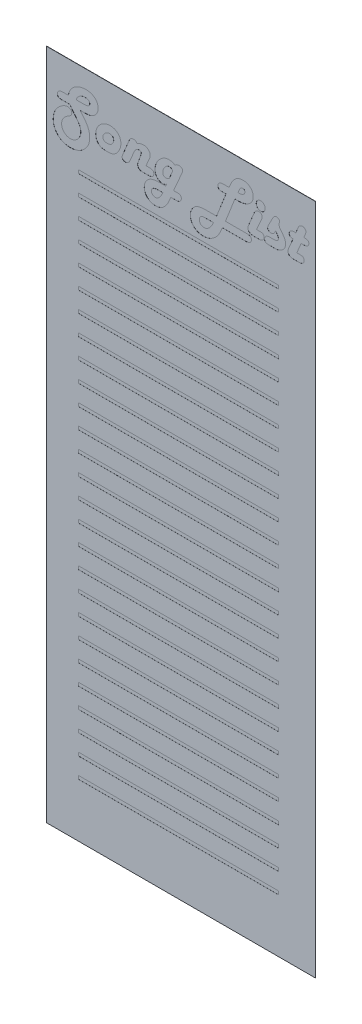
SolidWorks part; units mm, degrees
ref_plane "Front Plane" through (0, 0, 0) normal (0, 0, 1) x (1, 0, 0)
ref_plane "Top Plane" through (0, 0, 0) normal (0, 1, 0) x (1, 0, 0)
ref_plane "Right Plane" through (0, 0, 0) normal (1, 0, 0) x (0, 0, -1)
sketch "Sketch1" plane through (0, 0, 0) normal (0, 0, 1) x (1, 0, 0)
  line L1 (0, 0) -> (101.6, 0)
  line L2 (0, 0) -> (0, 254)
  line L3 (0, 254) -> (101.6, 254)
  line L4 (101.6, 0) -> (101.6, 254)
  dimension "D1" = 254
  dimension "D2" = 101.6
extrude "Boss-Extrude1" add sketch "Sketch1" along normal blind 0.0762
sketch "Sketch2" plane through (0, 0, 0.0762) normal (0, 0, 1) x (1, 0, 0)
  line L0 (12.1614, 212.0153) -> (87.7051, 212.0153)
  line L1 (12.1614, 219.6353) -> (87.7051, 219.6353)
  line L2 (12.1614, 219.6353) -> (12.1614, 218.3653)
  line L3 (12.1614, 218.3653) -> (87.7051, 218.3653)
  line L4 (87.7051, 219.6353) -> (87.7051, 218.3653)
  line L5 (12.1614, 212.0153) -> (12.1614, 210.7453)
  line L6 (87.7051, 212.0153) -> (87.7051, 210.7453)
  line L7 (12.1614, 210.7453) -> (87.7051, 210.7453)
  line L8 (12.1614, 204.3953) -> (87.7051, 204.3953)
  line L9 (12.1614, 204.3953) -> (12.1614, 203.1253)
  line L10 (87.7051, 204.3953) -> (87.7051, 203.1253)
  line L11 (12.1614, 203.1253) -> (87.7051, 203.1253)
  line L12 (12.1614, 196.7753) -> (87.7051, 196.7753)
  line L13 (12.1614, 196.7753) -> (12.1614, 195.5053)
  line L14 (87.7051, 196.7753) -> (87.7051, 195.5053)
  line L15 (12.1614, 195.5053) -> (87.7051, 195.5053)
  line L16 (12.1614, 189.1553) -> (87.7051, 189.1553)
  line L17 (12.1614, 189.1553) -> (12.1614, 187.8853)
  line L18 (87.7051, 189.1553) -> (87.7051, 187.8853)
  line L19 (12.1614, 187.8853) -> (87.7051, 187.8853)
  line L20 (12.1614, 181.5353) -> (87.7051, 181.5353)
  line L21 (12.1614, 181.5353) -> (12.1614, 180.2653)
  line L22 (87.7051, 181.5353) -> (87.7051, 180.2653)
  line L23 (12.1614, 180.2653) -> (87.7051, 180.2653)
  line L24 (12.1614, 173.9153) -> (87.7051, 173.9153)
  line L25 (12.1614, 173.9153) -> (12.1614, 172.6453)
  line L26 (87.7051, 173.9153) -> (87.7051, 172.6453)
  line L27 (12.1614, 172.6453) -> (87.7051, 172.6453)
  line L28 (12.1614, 166.2953) -> (87.7051, 166.2953)
  line L29 (12.1614, 166.2953) -> (12.1614, 165.0253)
  line L30 (87.7051, 166.2953) -> (87.7051, 165.0253)
  line L31 (12.1614, 165.0253) -> (87.7051, 165.0253)
  line L32 (12.1614, 158.6753) -> (87.7051, 158.6753)
  line L33 (12.1614, 158.6753) -> (12.1614, 157.4053)
  line L34 (87.7051, 158.6753) -> (87.7051, 157.4053)
  line L35 (12.1614, 157.4053) -> (87.7051, 157.4053)
  line L36 (12.1614, 151.0553) -> (87.7051, 151.0553)
  line L37 (12.1614, 151.0553) -> (12.1614, 149.7853)
  line L38 (87.7051, 151.0553) -> (87.7051, 149.7853)
  line L39 (12.1614, 149.7853) -> (87.7051, 149.7853)
  line L40 (12.1614, 143.4353) -> (87.7051, 143.4353)
  line L41 (12.1614, 143.4353) -> (12.1614, 142.1653)
  line L42 (87.7051, 143.4353) -> (87.7051, 142.1653)
  line L43 (12.1614, 142.1653) -> (87.7051, 142.1653)
  line L44 (12.1614, 135.8153) -> (87.7051, 135.8153)
  line L45 (12.1614, 135.8153) -> (12.1614, 134.5453)
  line L46 (87.7051, 135.8153) -> (87.7051, 134.5453)
  line L47 (12.1614, 134.5453) -> (87.7051, 134.5453)
  line L48 (12.1614, 128.1953) -> (87.7051, 128.1953)
  line L49 (12.1614, 128.1953) -> (12.1614, 126.9253)
  line L50 (87.7051, 128.1953) -> (87.7051, 126.9253)
  line L51 (12.1614, 126.9253) -> (87.7051, 126.9253)
  line L52 (12.1614, 120.5753) -> (87.7051, 120.5753)
  line L53 (12.1614, 120.5753) -> (12.1614, 119.3053)
  line L54 (87.7051, 120.5753) -> (87.7051, 119.3053)
  line L55 (12.1614, 119.3053) -> (87.7051, 119.3053)
  line L56 (12.1614, 112.9553) -> (87.7051, 112.9553)
  line L57 (12.1614, 112.9553) -> (12.1614, 111.6853)
  line L58 (87.7051, 112.9553) -> (87.7051, 111.6853)
  line L59 (12.1614, 111.6853) -> (87.7051, 111.6853)
  line L60 (12.1614, 105.3353) -> (87.7051, 105.3353)
  line L61 (12.1614, 105.3353) -> (12.1614, 104.0653)
  line L62 (87.7051, 105.3353) -> (87.7051, 104.0653)
  line L63 (12.1614, 104.0653) -> (87.7051, 104.0653)
  line L64 (12.1614, 97.7153) -> (87.7051, 97.7153)
  line L65 (12.1614, 97.7153) -> (12.1614, 96.4453)
  line L66 (87.7051, 97.7153) -> (87.7051, 96.4453)
  line L67 (12.1614, 96.4453) -> (87.7051, 96.4453)
  line L68 (12.1614, 90.0953) -> (87.7051, 90.0953)
  line L69 (12.1614, 90.0953) -> (12.1614, 88.8253)
  line L70 (87.7051, 90.0953) -> (87.7051, 88.8253)
  line L71 (12.1614, 88.8253) -> (87.7051, 88.8253)
  line L72 (12.1614, 82.4753) -> (87.7051, 82.4753)
  line L73 (12.1614, 82.4753) -> (12.1614, 81.2053)
  line L74 (87.7051, 82.4753) -> (87.7051, 81.2053)
  line L75 (12.1614, 81.2053) -> (87.7051, 81.2053)
  line L76 (12.1614, 74.8553) -> (87.7051, 74.8553)
  line L77 (12.1614, 74.8553) -> (12.1614, 73.5853)
  line L78 (87.7051, 74.8553) -> (87.7051, 73.5853)
  line L79 (12.1614, 73.5853) -> (87.7051, 73.5853)
  line L80 (12.1614, 67.2353) -> (87.7051, 67.2353)
  line L81 (12.1614, 67.2353) -> (12.1614, 65.9653)
  line L82 (87.7051, 67.2353) -> (87.7051, 65.9653)
  line L83 (12.1614, 65.9653) -> (87.7051, 65.9653)
  line L84 (12.1614, 59.6153) -> (87.7051, 59.6153)
  line L85 (12.1614, 59.6153) -> (12.1614, 58.3453)
  line L86 (87.7051, 59.6153) -> (87.7051, 58.3453)
  line L87 (12.1614, 58.3453) -> (87.7051, 58.3453)
  line L88 (12.1614, 51.9953) -> (87.7051, 51.9953)
  line L89 (12.1614, 51.9953) -> (12.1614, 50.7253)
  line L90 (87.7051, 51.9953) -> (87.7051, 50.7253)
  line L91 (12.1614, 50.7253) -> (87.7051, 50.7253)
  line L92 (12.1614, 44.3753) -> (87.7051, 44.3753)
  line L93 (12.1614, 44.3753) -> (12.1614, 43.1053)
  line L94 (87.7051, 44.3753) -> (87.7051, 43.1053)
  line L95 (12.1614, 43.1053) -> (87.7051, 43.1053)
  line L96 (12.1614, 36.7553) -> (87.7051, 36.7553)
  line L97 (12.1614, 36.7553) -> (12.1614, 35.4853)
  line L98 (87.7051, 36.7553) -> (87.7051, 35.4853)
  line L99 (12.1614, 35.4853) -> (87.7051, 35.4853)
  line L100 (12.1614, 29.1353) -> (87.7051, 29.1353)
  line L101 (12.1614, 29.1353) -> (12.1614, 27.8653)
  line L102 (87.7051, 29.1353) -> (87.7051, 27.8653)
  line L103 (12.1614, 27.8653) -> (87.7051, 27.8653)
  line L104 (12.1614, 21.5153) -> (87.7051, 21.5153)
  line L105 (12.1614, 21.5153) -> (12.1614, 20.2453)
  line L106 (87.7051, 21.5153) -> (87.7051, 20.2453)
  line L107 (12.1614, 20.2453) -> (87.7051, 20.2453)
  text T0 "Song List" font "Harlow Solid Italic" height 16.51
  point P5 (6.0707, 229.4522)
  point P6 (0, 0)
  dimension "D2" = 1.27
  dimension "D1" = 27
extrude "Cut-Extrude1" cut sketch "Sketch2" against normal blind 0.0254
